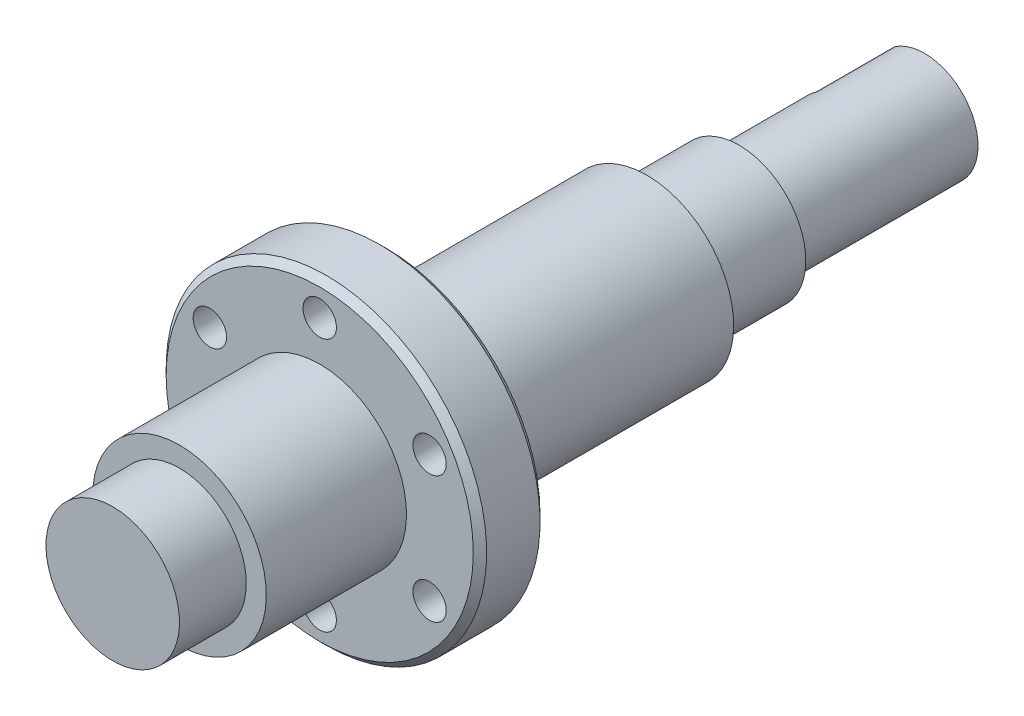
SolidWorks part; units mm, degrees
material "6061 合金"
ref_plane "前视基准面" through (0, 0, 0) normal (0, 0, 1) x (1, 0, 0)
ref_plane "上视基准面" through (0, 0, 0) normal (0, 1, 0) x (1, 0, 0)
ref_plane "右视基准面" through (0, 0, 0) normal (1, 0, 0) x (0, 0, -1)
sketch "草图1" plane through (0, 0, 0) normal (1, 0, 0) x (0, 0, -1)
  line L0 (0, 0) -> (0, 5)
  line L1 (0, 5) -> (5, 5)
  line L2 (5, 5) -> (5, 6.5)
  line L3 (5, 6.5) -> (15.5, 6.5)
  line L4 (15.5, 6.5) -> (15.5, 12)
  line L5 (15.5, 12) -> (20.5, 12)
  line L6 (20.5, 12) -> (20.5, 6.5)
  line L7 (20.5, 6.5) -> (40, 6.5)
  line L8 (40, 6.5) -> (40, 5)
  line L9 (40, 5) -> (54.9, 5)
  line L10 (54.9, 5) -> (54.9, 0)
  line L11 (54.9, 0) -> (0, 0) construction
  line L12 (0, 0) -> (54.9, 0)
  dimension "D1" = 10
  dimension "D2" = 5
  dimension "D3" = 1.5
  dimension "D4" = 15.5
  dimension "D5" = 24
  dimension "D6" = 5
  dimension "D7" = 19.5
  dimension "D8" = 14.9
revolve "旋转1" add sketch "草图1" angle 360 about L11
sketch "草图2" plane through (0, 0, -15.5) normal (0, 0, 1) x (1, 0, 0)
  circle A0 centre (0, 0) radius 9.5 construction
  circle A1 centre (0, 0) radius 6.5 construction
  dimension "D1" = 3
hole_wizard "M3 螺纹孔1" positions "草图3" profile "草图4" tap size "M3" standard "GB" end condition through all
sketch "草图3" plane through (0, 0, -15.5) normal (0, 0, 1) x (1, 0, 0)
  line L0 (0, 9.5) -> (0, 0) construction
  circle A0 centre (0, 0) radius 9.5 construction
  point P0 (0, 9.5)
sketch "草图4" plane through (0, 9.5, -15.5) normal (1, 0, 0) x (0, -1, 0)
  line L0 (0, 0) -> (0, 39.4)
  line L1 (0, 39.4) -> (1.25, 39.4)
  line L2 (1.25, 39.4) -> (1.25, 0)
  line L5 (1.25, 0) -> (0, 0)
  line L11 (0, -6.35) -> (0, 107.95) construction
  dimension "通孔螺纹孔钻头直径" = 2.5
  dimension "通孔螺纹孔钻头深度" = 39.4
cosmetic thread "孔螺蚊线1" parameters "D2"=3
pattern_circular "阵列(圆周)1" count 6 over 360 about axis through (0, 0, -54.9) along (0, 0, -1) of "M3 螺纹孔1"
cosmetic thread "孔螺蚊线2" parameters "D2"=3
cosmetic thread "孔螺蚊线3" parameters "D2"=3
cosmetic thread "孔螺蚊线4" parameters "D2"=3
cosmetic thread "孔螺蚊线5" parameters "D2"=3
cosmetic thread "孔螺蚊线6" parameters "D2"=3
chamfer "倒角1" distance 0.5 angle 45 2 edges at (0, 12, -15.5) (0, 12, -20.5)
sketch "草图5" plane through (0, 0, -54.9) normal (0, 0, -1) x (-1, 0, 0)
  circle A0 centre (0, 0) radius 4
  dimension "D1" = 8
extrude "切除-拉伸1" cut sketch "草图5" against normal blind 8 flip side to cut
sketch "草图6" plane through (0, 0, -54.9) normal (0, 0, -1) x (-1, 0, 0)
  line L0 (2.6, 3.0397) -> (2.6, -3.0397)
  circle A1 centre (0, 0) radius 4
  arc A2 (2.6, 3.0397) -> (2.6, -3.0397) centre (0, 0) ccw
  dimension "D2" = 2.6
  dimension "D1" = 0
extrude "凸台-拉伸1" add sketch "草图6" along normal blind 5.9
hole_wizard "M3 螺纹孔2" positions "草图8" profile "草图9" tap size "M3" standard "GB"
sketch "草图8" plane through (0, 0, -60.8) normal (0, 0, -1) x (-1, 0, 0)
  point P0 (0, 0)
sketch "草图9" plane through (0, 0, -60.8) normal (1, 0, 0) x (0, 1, 0)
  line L0 (0, 0) -> (0, 8.2511)
  line L1 (0, 8.2511) -> (1.25, 7.5)
  line L2 (1.25, 7.5) -> (1.25, 0)
  line L5 (1.25, 0) -> (0, 0)
  line L10 (0, 8.2511) -> (-1.25, 7.5) construction
  line L11 (0, -6.35) -> (0, 107.95) construction
  dimension "螺纹孔钻头直径" = 2.5
  dimension "螺纹孔钻头深度" = 7.5
  dimension "导头角度" = 118
cosmetic thread "孔螺蚊线7" parameters "D1"=6, "D2"=3
fillet "圆角1" radius 1 2 edges at (-2.6, -3.0397, -57.85) (-2.6, 3.0397, -57.85)
